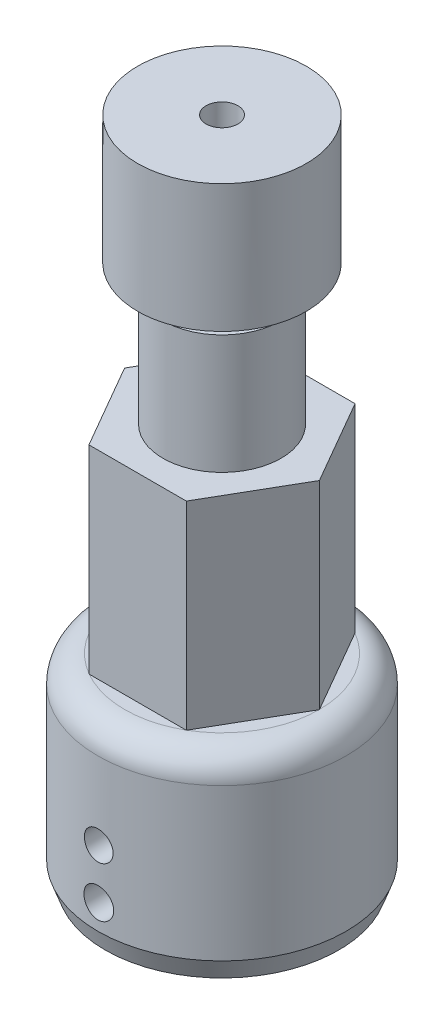
SolidWorks part; units mm, degrees
note: The reader was unsure of these and kept them because the rebuilt part matched: shared geometry of "Sketch1<2>", "Sketch6<2>".
ref_plane "Front Plane" through (0, 0, 0) normal (0, 0, 1) x (1, 0, 0)
ref_plane "Top Plane" through (0, 0, 0) normal (0, 1, 0) x (1, 0, 0)
ref_plane "Right Plane" through (0, 0, 0) normal (1, 0, 0) x (0, 0, -1)
sketch "Sketch1" plane through (0, 0, 0) normal (0, 1, 0) x (1, 0, 0)
  line L0 (-1.2, 1.408) -> (1.2, 1.408)
  line L1 (9.815, 0) -> (4.9075, 8.5)
  line L2 (4.9075, 8.5) -> (-4.9075, 8.5)
  line L3 (-4.9075, 8.5) -> (-9.815, 0)
  line L4 (-9.815, 0) -> (-4.9075, -8.5)
  line L5 (-4.9075, -8.5) -> (4.9075, -8.5)
  line L6 (4.9075, -8.5) -> (9.815, 0)
  circle A0 centre (0, 0) radius 8.5 construction
  circle A1 centre (0, 0) radius 5.95
  circle A2 centre (0, 0) radius 1.85
  dimension "D2" = 11.9
  dimension "D3" = 3.7
  dimension "D1" = 17
  dimension "D4" = 2.4
extrude "Boss-Extrude1" add sketch "Sketch1" along normal blind 40 contours L5 L6 L1 L2 L3 L4 A1
extrude "Boss-Extrude2" add sketch "Sketch1<2>" along normal blind 52 contours A1 A2 | L0 A2
sketch "Sketch1<2>" plane through (0, 0, 0) normal (0, 1, 0) x (1, 0, 0) same geometry as "Sketch1"
sketch "Sketch2" plane through (0, 0, 0) normal (0, -1, 0) x (1, 0, 0)
  circle A0 centre (0, 0) radius 12.5
  line M1 (4.9075, 8.5) -> (-4.9075, 8.5)
  line M2 (-4.9075, 8.5) -> (-9.815, 0)
  line M3 (-9.815, 0) -> (-4.9075, -8.5)
  line M4 (-4.9075, -8.5) -> (4.9075, -8.5)
  line M5 (4.9075, -8.5) -> (9.815, 0)
  line M6 (9.815, 0) -> (4.9075, 8.5)
  dimension "D1" = 25
extrude "Boss-Extrude3" add sketch "Sketch2" against normal blind 15 contours A0 M1 M6 M5 M4 M3 M2
sketch "Sketch3" plane through (0, 0, 0) normal (0, 0, 1) x (1, 0, 0)
  line L0 (0, 40) -> (0, 0) construction
  line L1 (4.9075, 40) -> (-4.9075, 40) construction
  line L2 (12.5, 15) -> (-12.5, 15) construction
  line L3 (12.5, 2.2) -> (-12.5, 2.2) construction
  circle A0 centre (0, 9.5) radius 1.45
  circle A1 centre (0, 4.5) radius 1.5
  dimension "D2" = 2.9
  dimension "D3" = 3
  dimension "D4" = 5
  dimension "D5" = 5.5
  dimension "D1" = 12.8
extrude "Cut-Extrude1" cut sketch "Sketch3" against normal through all both and the other way through all
sketch "Sketch5" plane through (0, 15, 0) normal (0, 1, 0) x (1, 0, 0)
  circle A1 centre (0, 0) radius 12.5
  circle A2 centre (0, 0) radius 12.5
  line M2 (4.9075, -8.5) -> (-4.9075, -8.5)
  line M3 (-4.9075, -8.5) -> (-9.815, 0)
  line M4 (-9.815, 0) -> (-4.9075, 8.5)
  line M5 (-4.9075, 8.5) -> (4.9075, 8.5)
  line M6 (4.9075, 8.5) -> (9.815, 0)
  line M7 (9.815, 0) -> (4.9075, -8.5)
  circle M8 centre (0, 0) radius 12.5
  dimension "D1" = 0
extrude "Boss-Extrude4" add sketch "Sketch5" along normal blind 5 contours M8 M7 M2 M3 M4 M5 M6
sketch "Sketch6" plane through (0, 52, 0) normal (0, 1, 0) x (1, 0, 0)
  circle A0 centre (0, 0) radius 1.85
  circle A1 centre (0, 0) radius 1.5
  line M2 (-1.2, 1.408) -> (1.2, 1.408)
  dimension "D1" = 3
sketch "Sketch7" plane through (0, 52, 0) normal (0, 1, 0) x (1, 0, 0)
  circle A0 centre (0, 0) radius 6
  circle A1 centre (0, 0) radius 8.5
  circle A3 centre (0, 0) radius 1.6
  dimension "D1" = 17
  dimension "D2" = 12
  dimension "D3" = 3.2
extrude "Boss-Extrude5" add sketch "Sketch7" along normal blind 15 separate body contours A1 A0
sketch "Sketch8" plane through (0, 67, 0) normal (0, 1, 0) x (1, 0, 0)
  circle A0 centre (0, 0) radius 6
  circle A1 centre (0, 0) radius 1.6
  dimension "D1" = 12
  dimension "D2" = 3.2
extrude "Boss-Extrude6" add sketch "Sketch8" against normal blind 3
sketch "Sketch9" plane through (0, 52, 0) normal (0, -1, 0) x (1, 0, 0)
  circle A1 centre (0, 0) radius 8.5
  circle A2 centre (0, 0) radius 8.5
  dimension "D1" = 0
extrude "Cut-Extrude4" cut sketch "Sketch9" against normal blind 2.1
extrude "Boss-Extrude7" add sketch "Sketch6" against normal blind 20
extrude "Cut-Extrude5" cut sketch "Sketch6<2>" against normal blind 20 contours A1 M2
sketch "Sketch6<2>" plane through (0, 52, 0) normal (0, 1, 0) x (1, 0, 0) same geometry as "Sketch6"
chamfer "Chamfer1" distance 1 angle 20 1 edges at (0, 32, 1.5) first distance on face at (0, 32, 0)
fillet "Fillet1" radius 2.7 1 edges at (0, 20, 12.5)
chamfer "Chamfer2" distance 2 angle 20 1 edges at (0, 0, -12.5) first distance on face at (0, 17.3, 12.5)
